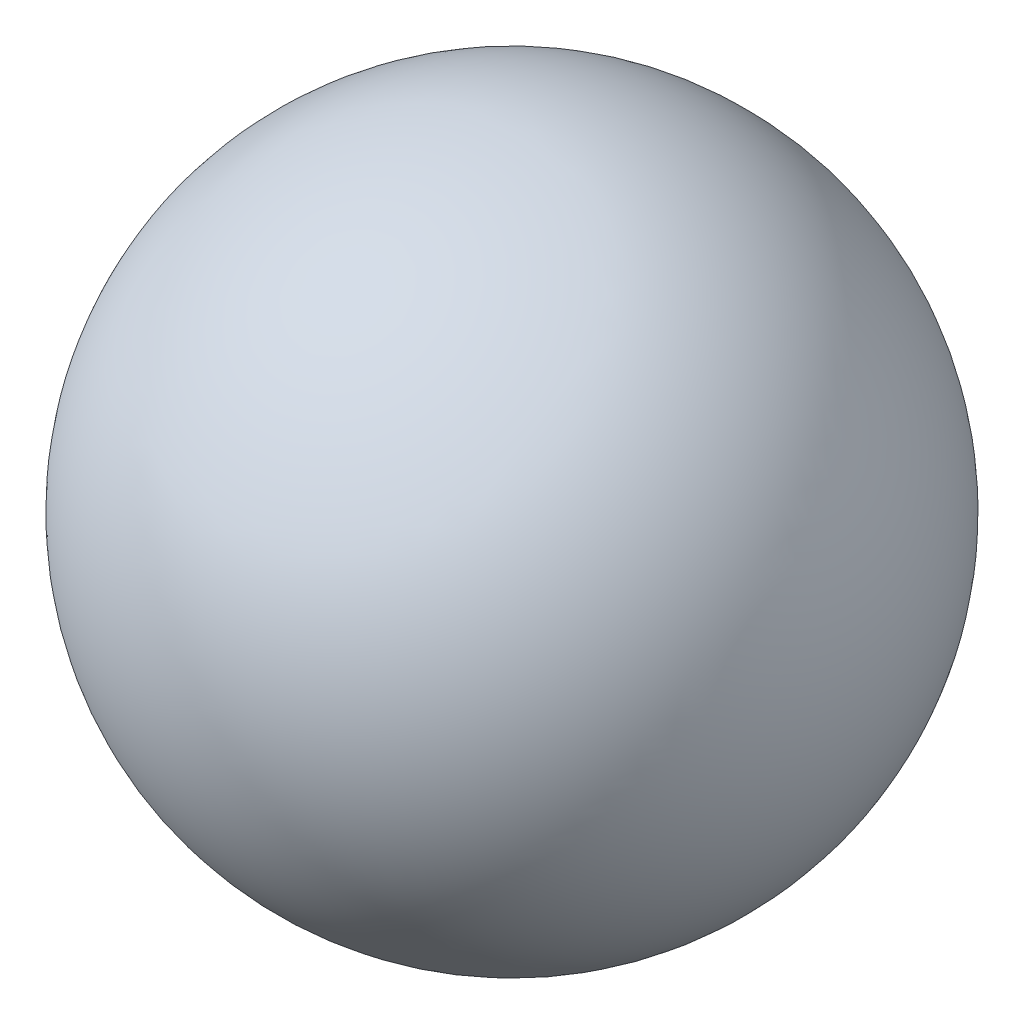
SolidWorks part; units mm, degrees
ref_plane "前基準面" through (0, 0, 0) normal (0, 0, 1) x (1, 0, 0)
ref_plane "上基準面" through (0, 0, 0) normal (0, 1, 0) x (1, 0, 0)
ref_plane "右基準面" through (0, 0, 0) normal (1, 0, 0) x (0, 0, -1)
sketch "草圖1" plane through (0, 0, 0) normal (0, 0, 1) x (1, 0, 0)
  line L0 (-7.5, 0) -> (7.5, 0)
  circle A0 centre (0, 0) radius 7.5
  point P5 (0, 0)
revolve "旋轉2" add sketch "草圖1" angle 360 about L0 region at (0, 3.1831, 0)
